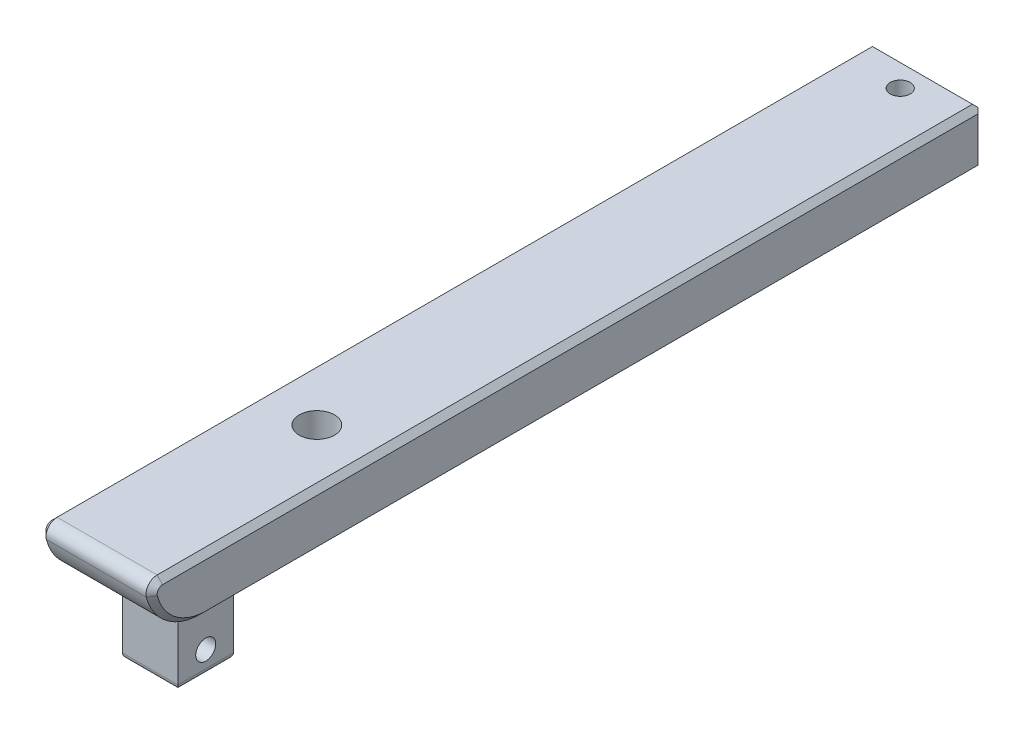
SolidWorks part; units mm, degrees
ref_plane "Front Plane" through (0, 0, 0) normal (0, 0, 1) x (1, 0, 0)
ref_plane "Top Plane" through (0, 0, 0) normal (0, 1, 0) x (1, 0, 0)
ref_plane "Right Plane" through (0, 0, 0) normal (1, 0, 0) x (0, 0, -1)
sketch "Sketch1" plane through (0, 0, 0) normal (0, 1, 0) x (1, 0, 0)
  line L1 (0, 0) -> (20, 0)
  line L2 (0, 0) -> (0, 150)
  line L3 (0, 150) -> (20, 150)
  line L4 (20, 0) -> (20, 150)
  dimension "D1" = 20
  dimension "D2" = 150
extrude "Boss-Extrude1" add sketch "Sketch1" along normal blind 10
hole_wizard "M3 Clearance Hole1" positions "3DSketch1" profile "Sketch2" hole size "M3" standard "ANSI Metric" end condition through all
sketch3d "3DSketch1"
  line L0 (20, 0, -150) -> (0, 0, -150) construction
  line L1 (20, 0, 0) -> (20, 0, -150) construction
  point P0 (10, 0, -145)
  dimension "D1" = 5
  dimension "D2" = 10
sketch "Sketch2" plane through (10, 0, -145) normal (1, 0, 0) x (0, 0, -1)
  line L0 (0, 0) -> (0, 10)
  line L1 (0, 10) -> (1.8, 10)
  line L2 (1.8, 10) -> (1.8, 0)
  line L5 (1.8, 0) -> (0, 0)
  line L11 (0, -6.35) -> (0, 107.95) construction
  dimension "Thru Hole Dia." = 3.6
  dimension "Thru Hole Depth" = 10
sketch "Sketch3" plane through (0, 0, 0) normal (0, -1, 0) x (1, 0, 0)
  line L0 (0, -150) -> (0, 0) construction
  line L1 (5, -10) -> (15, -10)
  line L2 (5, -10) -> (5, -20)
  line L3 (5, -20) -> (15, -20)
  line L4 (15, -10) -> (15, -20)
  line L5 (0, 0) -> (20, 0) construction
  dimension "D1" = 10
  dimension "D2" = 5
  dimension "D3" = 10
  dimension "D4" = 10
extrude "Boss-Extrude2" add sketch "Sketch3" along normal blind 14
hole_wizard "M3 Clearance Hole5" positions "3DSketch5" profile "Sketch7" hole size "M3" standard "ANSI Metric" end condition through all
sketch3d "3DSketch5"
  line L0 (5, -14, -10) -> (5, -14, -20) construction
  line L1 (5, -14, -20) -> (5, 0, -20) construction
  point P0 (5, -10, -15)
  dimension "D1" = 4
  dimension "D2" = 5
sketch "Sketch7" plane through (5, -10, -15) normal (0, 1, 0) x (0, 0, 1)
  line L0 (0, 0) -> (0, 15)
  line L1 (0, 15) -> (1.8, 15)
  line L2 (1.8, 15) -> (1.8, 0)
  line L5 (1.8, 0) -> (0, 0)
  line L11 (0, -6.35) -> (0, 107.95) construction
  dimension "Thru Hole Dia." = 3.6
  dimension "Thru Hole Depth" = 15
hole_wizard "1/4 (0.25) Diameter Hole1" positions "3DSketch6" profile "Sketch8" hole size "1/4" standard "ANSI Inch" end condition up to next
sketch3d "3DSketch6"
  line L0 (20, 0, -150) -> (0, 0, -150) construction
  line L1 (20, 0, 0) -> (20, 0, -150) construction
  point P0 (10, 0, -40)
  dimension "D1" = 110
  dimension "D2" = 10
sketch "Sketch8" plane through (10, 0, -40) normal (1, 0, 0) x (0, 0, -1)
  line L0 (0, 0) -> (0, 10)
  line L1 (0, 10) -> (3.175, 10)
  line L2 (3.175, 10) -> (3.175, 0)
  line L5 (3.175, 0) -> (0, 0)
  line L11 (0, -6.35) -> (0, 107.95) construction
  dimension "Thru Hole Dia." = 6.35
  dimension "Thru Hole Depth" = 10
fillet "Fillet1" radius 10 1 edges at (10, 0, 0)
fillet "Fillet2" radius 2 1 edges at (10, 10, 0)
chamfer "Chamfer1" distance 1 angle 45 10 edges at (20, 5, -150) (20, 0, -80) (20, 2.0943, -3.8763) (20, 9.2247, -0.6729) (20, 10, -76.127) (0, 0, -80) (0, 5, -150) (0, 10, -76.127) (0, 9.2247, -0.6729) (0, 2.0943, -3.8763)
fillet "Fillet3" radius 1 4 edges at (10, -14, -20) (5, -14, -15) (10, -14, -10) (15, -14, -15)
chamfer "Chamfer2" distance 1 angle 45 2 edges at (10, 10, -150) (10, 0, -150)
